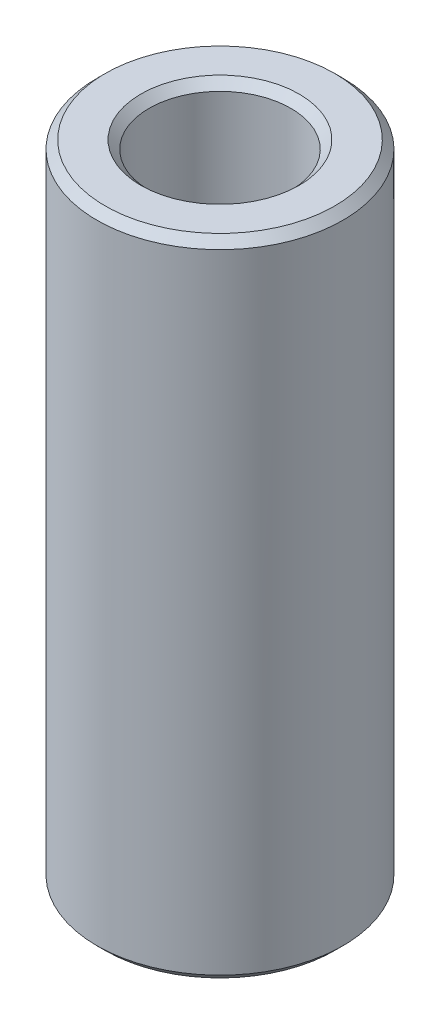
SolidWorks part; units mm, degrees
ref_plane "Front Plane" through (0, 0, 0) normal (0, 0, 1) x (1, 0, 0)
ref_plane "Top Plane" through (0, 0, 0) normal (0, 1, 0) x (1, 0, 0)
ref_plane "Right Plane" through (0, 0, 0) normal (1, 0, 0) x (0, 0, -1)
sketch "Sketch1" plane through (0, 0, 0) normal (0, 1, 0) x (1, 0, 0)
  circle A0 centre (0, 0) radius 40
  dimension "SLEEVE_OD" = 80
extrude "Boss-Extrude1" add sketch "Sketch1" along normal blind 209.6447
sketch "Sketch2" plane through (0, 0, 0) normal (0, 1, 0) x (1, 0, 0)
  circle A0 centre (0, 0) radius 23.0597
  dimension "BORE_D" = 46.1194
extrude "Cut-Extrude1" cut sketch "Sketch2" along normal through all
chamfer "Chamfer1" distance 2.6804 angle 45 4 edges at (0, 209.6447, 23.0597) (0, 0, 23.0597) (0, 0, 40) (0, 209.6447, 40)
